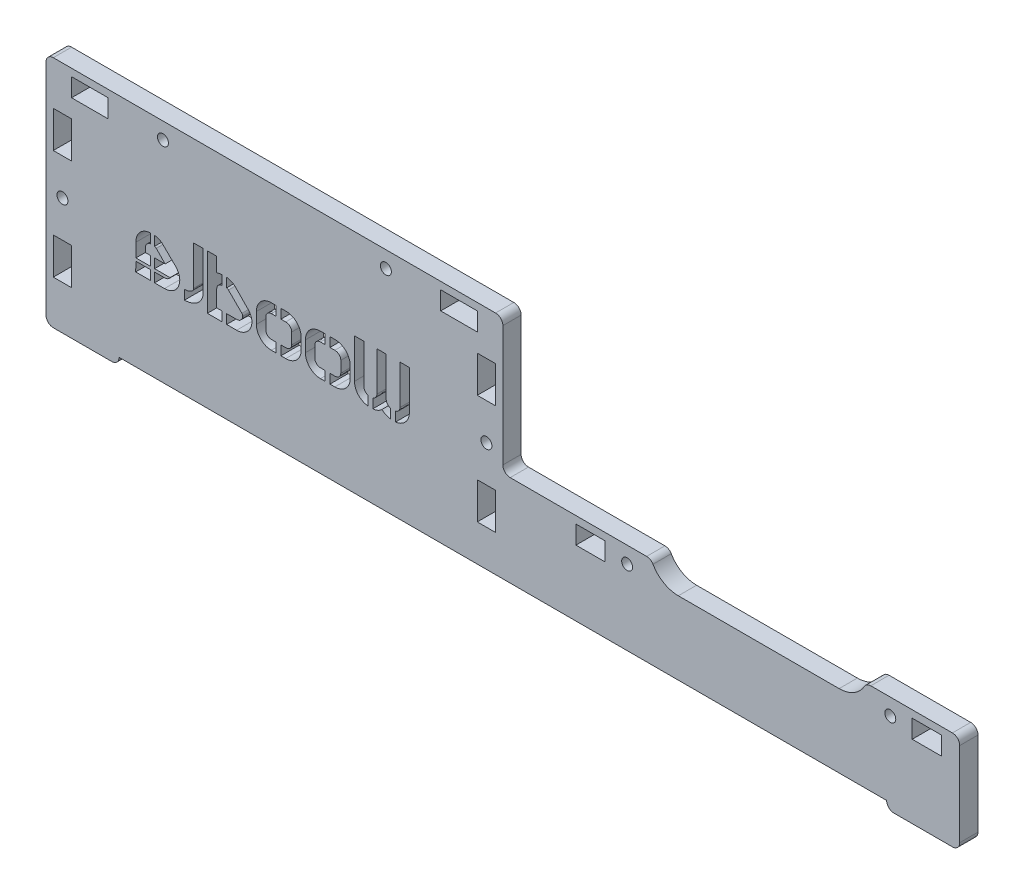
SolidWorks part; units mm, degrees
material "Maple"
ref_plane "Front Plane" through (0, 0, 0) normal (0, 0, 1) x (1, 0, 0)
ref_plane "Top Plane" through (0, 0, 0) normal (0, 1, 0) x (1, 0, 0)
ref_plane "Right Plane" through (0, 0, 0) normal (1, 0, 0) x (0, 0, -1)
sketch "Sketch1" plane through (0, 0, 0) normal (0, 0, 1) x (1, 0, 0)
  line L0 (0, 0) -> (0, 64)
  line L1 (0, 64) -> (125, 64)
  line L2 (125, 64) -> (125, 27)
  line L3 (125, 27) -> (250, 27)
  line L4 (250, 27) -> (250, 0)
  line L5 (250, 0) -> (0, 0)
  dimension "D1" = 64
  dimension "D2" = 125
  dimension "D3" = 125
  dimension "D4" = 27
extrude "Boss-Extrude1" add sketch "Sketch1" along normal blind 5
sketch "Sketch2" plane through (0, 0, 5) normal (0, 0, 1) x (1, 0, 0)
  line L0 (0, 64) -> (0, 0) construction
  line L1 (7, 62) -> (17, 62)
  line L2 (7, 62) -> (7, 57)
  line L3 (7, 57) -> (17, 57)
  line L4 (17, 62) -> (17, 57)
  line L5 (108, 62) -> (118, 62)
  line L6 (108, 62) -> (108, 57)
  line L7 (108, 57) -> (118, 57)
  line L8 (118, 62) -> (118, 57)
  line L9 (125, 64) -> (0, 64) construction
  line L10 (125, 27) -> (125, 64) construction
  line L11 (250, 27) -> (125, 27) construction
  line L12 (245, 25) -> (237, 25)
  line L13 (245, 25) -> (245, 20)
  line L14 (245, 20) -> (237, 20)
  line L15 (237, 25) -> (237, 20)
  line L16 (145, 25) -> (153, 25)
  line L17 (145, 25) -> (145, 20)
  line L18 (145, 20) -> (153, 20)
  line L19 (153, 25) -> (153, 20)
  line L20 (250, 0) -> (250, 27) construction
  line L21 (173, 30) -> (217, 30) construction
  line L22 (153, 20) -> (237, 20) construction
  line L23 (62.5, 64) -> (62.5, 0) construction
  line L24 (123, 52) -> (118, 52)
  line L25 (123, 52) -> (123, 42)
  line L26 (123, 42) -> (118, 42)
  line L27 (118, 52) -> (118, 42)
  line L28 (123, 22) -> (118, 22)
  line L29 (123, 22) -> (123, 12)
  line L30 (123, 12) -> (118, 12)
  line L31 (118, 22) -> (118, 12)
  line L32 (7, 22) -> (7, 12)
  line L33 (2, 12) -> (7, 12)
  line L34 (2, 22) -> (2, 12)
  line L35 (2, 22) -> (7, 22)
  line L36 (7, 52) -> (7, 42)
  line L37 (2, 42) -> (7, 42)
  line L38 (2, 52) -> (2, 42)
  line L39 (2, 52) -> (7, 52)
  line L40 (0, 0) -> (250, 0) construction
  line L41 (173, 22) -> (217, 22)
  line L42 (173, 38) -> (217, 38)
  line L43 (159, 22.5) -> (153, 22.5) construction
  line L44 (195, 20) -> (195, 7) construction
  line L45 (120.5, 22) -> (120.5, 42) construction
  line L46 (108, 59.5) -> (93, 59.5) construction
  arc A0 (173, 38) -> (173, 22) centre (173, 30) ccw
  arc A1 (217, 22) -> (217, 38) centre (217, 30) ccw
  circle A2 centre (159, 22.5) radius 1.5
  circle A3 centre (231, 22.5) radius 1.5
  circle A4 centre (120.5, 32) radius 1.5
  circle A5 centre (4.5, 32) radius 1.5
  circle A6 centre (93, 59.5) radius 1.5
  circle A7 centre (32, 59.5) radius 1.5
  point P29 (165, 30)
  point P38 (120.5, 52)
  point P55 (225, 30)
  dimension "D9" = 20
  dimension "D10" = 16
  dimension "D18" = 3
  dimension "D19" = 3
  dimension "D1" = 7
  dimension "D2" = 2
  dimension "D3" = 5
  dimension "D4" = 10
  dimension "D5" = 7
  dimension "D6" = 2
  dimension "D7" = 100
  dimension "D8" = 5
  dimension "D11" = 10
  dimension "D12" = 20
  dimension "D13" = 8
  dimension "D14" = 40
  dimension "D15" = 10
  dimension "D16" = 2
  dimension "D17" = 14
  dimension "D20" = 30
extrude "Cut-Extrude1" cut sketch "Sketch2" against normal through all
sketch "Sketch4" plane through (0, 0, 5) normal (0, 0, 1) x (1, 0, 0)
  line L0 (0, 0) -> (250, 0) construction
  line L1 (20, 0) -> (230, 0)
  line L2 (20, 0) -> (20, 2)
  line L3 (20, 2) -> (230, 2)
  line L4 (230, 0) -> (230, 2)
  line L5 (250, 0) -> (250, 27) construction
  line L6 (0, 64) -> (0, 0) construction
  dimension "D1" = 2
  dimension "D2" = 20
  dimension "D3" = 20
extrude "Cut-Extrude3" cut sketch "Sketch4" against normal through all
sketch "Sketch3" plane through (0, 0, 5) normal (0, 0, 1) x (1, 0, 0)
  line L0 (0, 64) -> (0, 0) construction
  line L1 (19.17, 38.85) -> (31.17, 38.85) construction
  line L2 (19.17, 38.85) -> (19.17, 49.35) construction
  line L3 (19.17, 49.35) -> (31.17, 49.35) construction
  line L4 (31.17, 38.85) -> (31.17, 49.35) construction
  line L6 (125, 64) -> (0, 64) construction
  line L7 (18.17, 37.85) -> (32.17, 37.85)
  line L8 (32.17, 37.85) -> (32.17, 50.35)
  line L9 (18.17, 50.35) -> (32.17, 50.35)
  line L10 (18.17, 37.85) -> (18.17, 50.35)
  line L11 (46.31, 28.01) -> (46.31, 21.31) construction
  line L12 (46.31, 36.51) -> (68.63, 36.51) construction
  line L13 (46.31, 36.51) -> (46.31, 28.01) construction
  line L14 (46.31, 28.01) -> (68.63, 28.01) construction
  line L15 (68.63, 36.51) -> (68.63, 28.01) construction
  line L16 (46.31, 21.31) -> (68.63, 21.31) construction
  line L17 (68.63, 21.31) -> (68.63, 28.01) construction
  line L18 (45.31, 37.51) -> (45.31, 28.01)
  line L19 (45.31, 28.01) -> (45.31, 20.31)
  line L20 (45.31, 20.31) -> (69.63, 20.31)
  line L21 (69.63, 20.31) -> (69.63, 28.01)
  line L22 (69.63, 37.51) -> (69.63, 28.01)
  line L23 (45.31, 37.51) -> (69.63, 37.51)
  point P6 (19.17, 44.1)
  dimension "D1" = 19.17
  dimension "D2" = 14.65
  dimension "D3" = 10.5
  dimension "D4" = 12
  dimension "D6" = 15.14
  dimension "D7" = 10.84
  dimension "D8" = 22.32
  dimension "D9" = 8.5
  dimension "D10" = 15.2
  dimension "D5" = 1
  dimension "D11" = 1
fillet "Fillet1" radius 2 10 edges at (250, 0, 2.5) (250, 27, 2.5) (0, 0, 2.5) (125, 64, 2.5) (0, 64, 2.5) (125, 27, 2.5) (224.4162, 27, 2.5) (165.5838, 27, 2.5) (230, 0, 2.5) (20, 0, 2.5)
sketch "Sketch5" plane through (0, 0, 5) normal (0, 0, 1) x (1, 0, 0)
  line L0 (100, 24.5) -> (25, 24.5) construction
  line L1 (100, 24.5) -> (100, 39.5) construction
  line L2 (100, 39.5) -> (25, 39.5) construction
  line L3 (25, 39.5) -> (25, 24.5) construction
  line L4 (108, 57) -> (17, 57) construction
  line L5 (120.5, 32) -> (100, 32) construction
  line L6 (25, 32) -> (4.5, 32) construction
  text T0 "Woodle" font "Sylar Stencil" height 15
  dimension "D1" = 75
  dimension "D2" = 15
extrude "Cut-Extrude4" cut sketch "Sketch5" against normal through all
